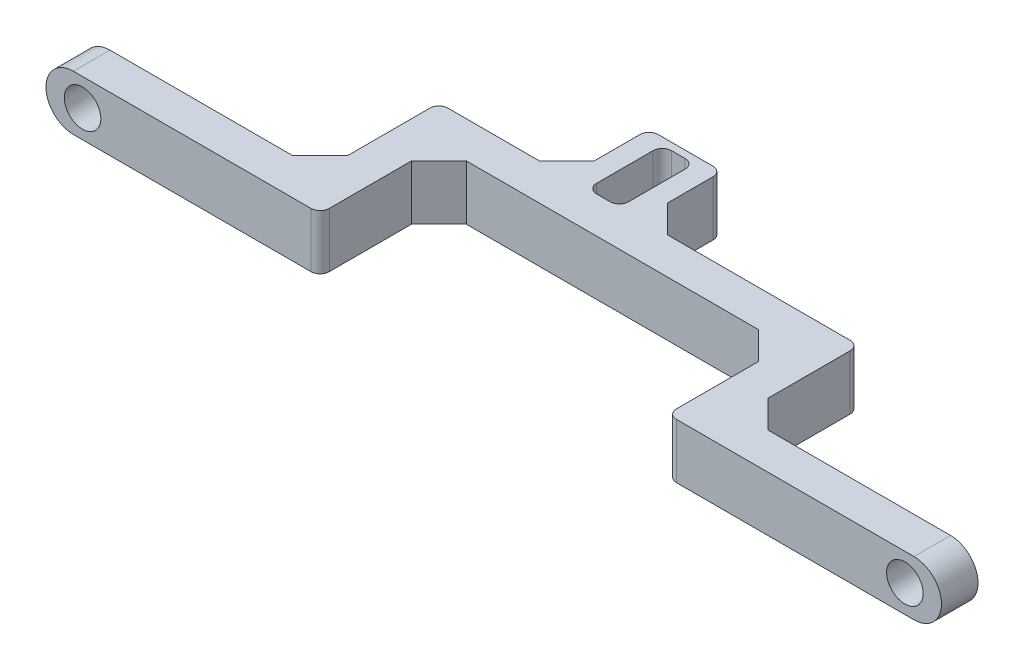
SolidWorks part; units mm, degrees
ref_plane "Alzado" through (0, 0, 0) normal (0, 0, 1) x (1, 0, 0)
ref_plane "Planta" through (0, 0, 0) normal (0, 1, 0) x (1, 0, 0)
ref_plane "Vista lateral" through (0, 0, 0) normal (1, 0, 0) x (0, 0, -1)
sketch "Croquis1" plane through (0, 0, 0) normal (0, 0, 1) x (1, 0, 0)
  line L0 (0, 0) -> (90, 0) construction
  circle A0 centre (0, 0) radius 3
  circle A1 centre (90, 0) radius 3
  dimension "D1" = 6
  dimension "D2" = 6
  dimension "D3" = 90
extrude "Saliente-Extruir1" add sketch "Croquis1" along normal blind 4
sketch "Croquis2" plane through (0, 0, 0) normal (0, 0, 1) x (1, 0, 0)
  line L1 (0, -3) -> (90, -3)
  line L2 (0, -3) -> (0, 3)
  line L3 (0, 3) -> (90, 3)
  line L4 (90, -3) -> (90, 3)
  circle A0 centre (0, 0) radius 3 construction
  circle A1 centre (90, 0) radius 3 construction
  dimension "D1" = 90
  dimension "D2" = 6
extrude "Saliente-Extruir2" add sketch "Croquis2" along normal blind 4
sketch "Croquis4" plane through (0, 3, 0) normal (0, 1, 0) x (1, 0, 0)
  line L1 (22, 13) -> (68, 13)
  line L2 (22, 13) -> (22, 0)
  line L3 (22, 0) -> (68, 0)
  line L4 (68, 13) -> (68, 0)
  line L5 (90, 0) -> (0, 0) construction
  line L7 (90, -4) -> (0, -4) construction
  point P5 (45, 0)
  point P6 (45, 0)
  dimension "D1" = 22
  dimension "D2" = 17
extrude "Saliente-Extruir3" add sketch "Croquis4" against normal blind 6
sketch "Croquis5" plane through (0, 3, 0) normal (0, 1, 0) x (1, 0, 0)
  line L0 (90, -4) -> (0, -4) construction
  line L1 (26, -4) -> (64, -4)
  line L2 (26, -4) -> (26, 9)
  line L3 (26, 9) -> (64, 9)
  line L4 (64, -4) -> (64, 9)
  line L5 (68, 13) -> (22, 13) construction
  line L6 (22, 13) -> (22, 0) construction
  line L7 (68, 0) -> (68, 13) construction
  point P12 (68, 6.5)
  dimension "D1" = 4
  dimension "D2" = 4
  dimension "D3" = 4
extrude "Cortar-Extruir1" cut sketch "Croquis5" against normal through all
sketch "Croquis6" plane through (0, 0, 0) normal (0, 1, 0) x (1, 0, 0)
  line L0 (68, 13) -> (22, 13) construction
  line L2 (36, 22) -> (44, 22)
  line L3 (36, 22) -> (36, 13)
  line L4 (36, 13) -> (44, 13)
  line L5 (44, 22) -> (44, 13)
  point P0 (45, 13)
  point P1 (40, 13)
  dimension "D1" = 5
  dimension "D2" = 9
  dimension "D3" = 8
extrude "Saliente-Extruir4" add sketch "Croquis6" against normal mid plane 6
sketch "Croquis7" plane through (0, 3, 0) normal (0, 1, 0) x (1, 0, 0)
  line L0 (40, 21.2) -> (40, 22) construction
  line L1 (38.25, 21.2) -> (41.75, 21.2)
  line L2 (38.25, 21.2) -> (38.25, 13)
  line L3 (38.25, 13) -> (41.75, 13)
  line L4 (41.75, 21.2) -> (41.75, 13)
  line L5 (44, 22) -> (36, 22) construction
  line L6 (36, 13) -> (22, 13) construction
  dimension "D1" = 0.8
  dimension "D2" = 3.5
extrude "Cortar-Extruir2" cut sketch "Croquis7" against normal through all
chamfer "Chaflán1" distance 3 angle 45 6 edges at (68, 0, 0) (22, 0, 0) (26, 0, -9) (64, 0, -9) (36, 0, -13) (44, 0, -13)
fillet "Redondeo1" radius 1 10 edges at (41.75, 0, -13) (38.25, 0, -13) (38.25, 0, -21.2) (41.75, 0, -21.2) (68, 0, -13) (64, 0, 4) (26, 0, 4) (22, 0, -13) (36, 0, -22) (44, 0, -22)
sketch "Croquis8" plane through (0, 0, 4) normal (0, 0, 1) x (1, 0, 0)
  circle A0 centre (0, 0) radius 1.75
  circle A1 centre (90, 0) radius 1.75
  dimension "D1" = 3.5
  dimension "D2" = 3.5
extrude "Cortar-Extruir3" cut sketch "Croquis8" against normal through all
ref_plane "Plano1" through (45, 0, 0) normal (1, 0, 0) x (0, 0, -1)
sketch "Croquis9" plane through (0, 0, 4) normal (0, 0, 1) x (1, 0, 0)
  line L0 (-1, 3) -> (0, 3)
  line L1 (-1, -3) -> (0, -3)
  line L2 (0, 2.5) -> (0, 3)
  line L3 (0, -3) -> (0, -2.5)
  arc A0 (-1, 3) -> (-1, -3) centre (-1, 0) ccw
  arc A1 (0, 2.5) -> (0, -2.5) centre (0, 0) ccw
  dimension "D1" = 1
  dimension "D2" = 5
extrude "Saliente-Extruir5" add sketch "Croquis9" against normal blind 4
mirror "Simetría1" about plane through (45, 0, 0) normal (1, 0, 0) of "Saliente-Extruir5"
sketch "Croquis10" plane through (0, 0, 0) normal (0, 0, -1) x (-1, 0, 0)
  circle A3 centre (0, 0) radius 2
  circle A6 centre (-90, 0) radius 2
  dimension "D1" = 4
extrude "Cortar-Extruir4" cut sketch "Croquis10" against normal through all
